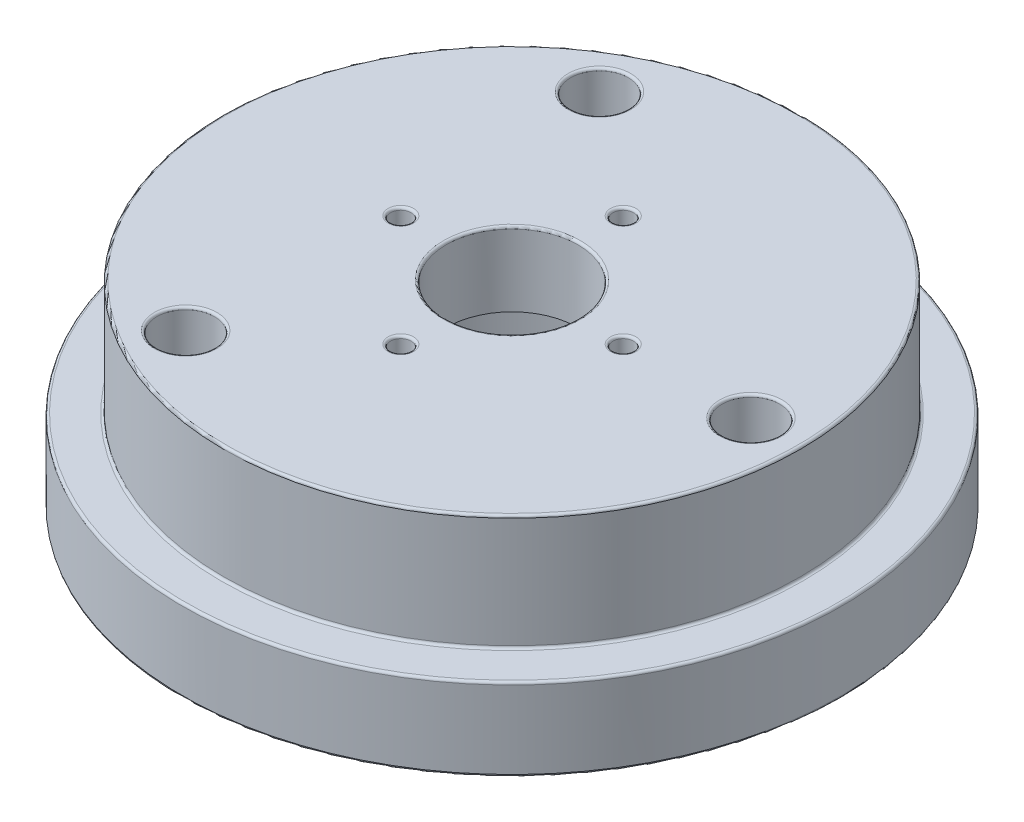
SolidWorks part; units mm, degrees
ref_plane "Front Plane" through (0, 0, 0) normal (0, 0, 1) x (1, 0, 0)
ref_plane "Top Plane" through (0, 0, 0) normal (0, 1, 0) x (1, 0, 0)
ref_plane "Right Plane" through (0, 0, 0) normal (1, 0, 0) x (0, 0, -1)
sketch "Sketch1" plane through (0, 0, 0) normal (0, 0, 1) x (1, 0, 0)
  line L0 (0, 0) -> (-20, 0)
  line L1 (-20, 0) -> (-20, 5)
  line L2 (-20, 5) -> (-17.5, 5)
  line L3 (-17.5, 5) -> (-17.5, 12)
  line L4 (-17.5, 12) -> (0, 12)
  line L5 (0, 12) -> (0, 0)
  dimension "D1" = 20
  dimension "D2" = 5
  dimension "D3" = 12
  dimension "D4" = 17.5
revolve "Revolve1" add sketch "Sketch1" angle 360 about L5
sketch "Sketch2" plane through (0, 0, 0) normal (0, -1, 0) x (1, 0, 0)
  circle A0 centre (0, 0) radius 10
  circle A1 centre (14.5, 0) radius 1.75
  circle A2 centre (-7.25, -12.5574) radius 1.75
  circle A3 centre (-7.25, 12.5574) radius 1.75
  circle A4 centre (0, 0) radius 20 construction
  circle A5 centre (0, 0) radius 4
  circle A10 centre (6.75, 0) radius 0.625
  circle A11 centre (0, -6.75) radius 0.625
  circle A12 centre (-6.75, 0) radius 0.625
  circle A13 centre (0, 6.75) radius 0.625
  point P12 (0, 0)
  point P24 (-0.125, 0.125)
  point P25 (0, 0)
  dimension "D1" = 20
  dimension "D2" = 3.5
  dimension "D7" = 8
  dimension "D8" = 6.75
  dimension "D10" = 4
  dimension "D9" = 1.25
  dimension "D3" = 14.5
  dimension "D5" = 14.5
  dimension "D6" = 7.25
  dimension "D4" = 3
extrude "Cut-Extrude1" cut sketch "Sketch2" against normal through all contours A12 | A3 | A2 | A11 | A10 | A13 | A1 | A5
extrude "Cut-Extrude2" cut sketch "Sketch2<3>" against normal blind 7.5
sketch "Sketch2<3>" plane through (0, 0, 0) normal (0, -1, 0) x (1, 0, 0) same geometry as "Sketch2"
fillet "Fillet2" radius 0.15 8 edges at (-17.5, 12, 0) (-20, 5, 0) (-17.5, 5, 0) (-20, 0, 0) (16.25, 0, 0) (-5.5, 0, -12.5574) (-5.5, 0, 12.5574) (10, 0, 0)
fillet "Fillet3" radius 0.15 9 edges at (-6.125, 12, 0) (0.625, 12, 6.75) (16.25, 12, 0) (4, 12, 0) (7.375, 12, 0) (0.625, 12, -6.75) (-5.5, 12, -12.5574) (-5.5, 12, 12.5574) (10, 7.5, 0)
